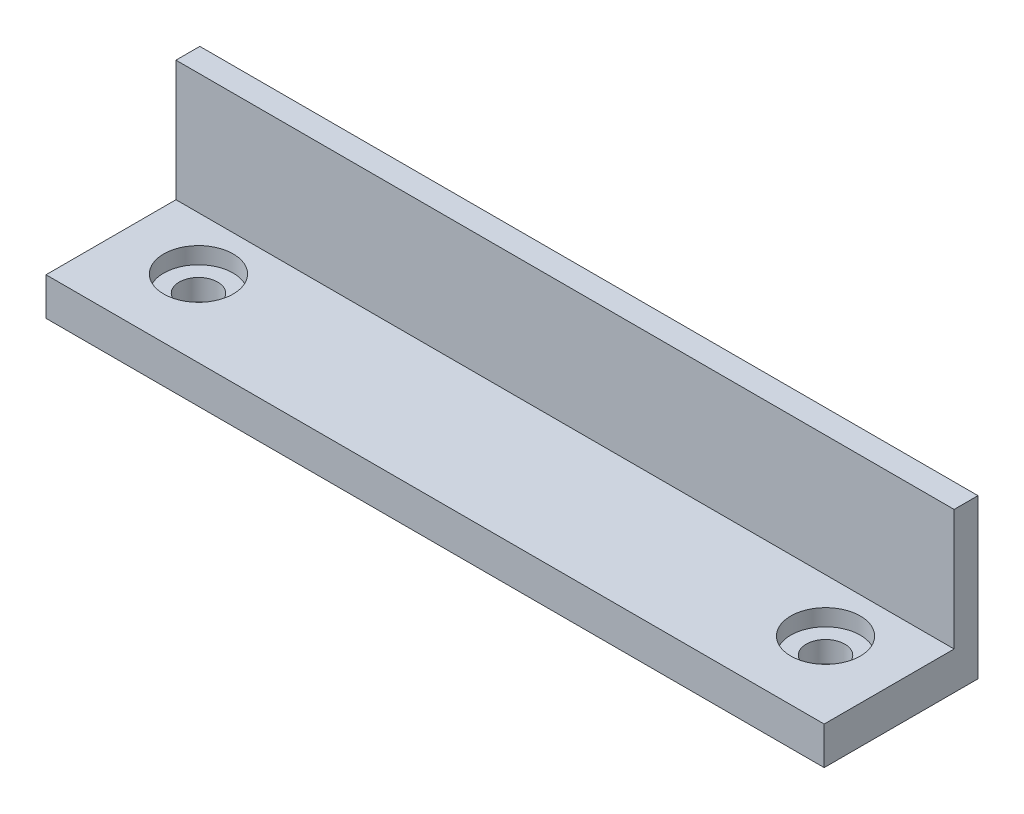
SolidWorks part; units mm, degrees
ref_plane "Front Plane" through (0, 0, 0) normal (0, 0, 1) x (1, 0, 0)
ref_plane "Top Plane" through (0, 0, 0) normal (0, 1, 0) x (1, 0, 0)
ref_plane "Right Plane" through (0, 0, 0) normal (1, 0, 0) x (0, 0, -1)
sketch "Sketch1" plane through (0, 0, 0) normal (0, 1, 0) x (1, 0, 0)
  line L0 (-51.5, 7.02) -> (51.5, 7.02)
  line L1 (-51.5, -10.18) -> (51.5, -10.18)
  line L2 (-51.5, -10.18) -> (-51.5, 10.18)
  line L3 (-51.5, 10.18) -> (51.5, 10.18)
  line L4 (51.5, -10.18) -> (51.5, 10.18)
  line L5 (-51.5, -10.18) -> (51.5, 10.18) construction
  line L6 (-51.5, 10.18) -> (51.5, -10.18) construction
  line L7 (0, 18.105) -> (0, -20.0728) construction
  circle A0 centre (41.5, 0) radius 2.55
  circle A1 centre (41.5, 0) radius 4.6
  circle A2 centre (-41.5, 0) radius 2.55
  circle A3 centre (-41.5, 0) radius 4.6
  point P0 (0, 0)
  dimension "D4" = 10
  dimension "D5" = 10.18
  dimension "D6" = 5.1
  dimension "D7" = 9.2
  dimension "D1" = 103
  dimension "D2" = 20.36
  dimension "D3" = 3.16
extrude "Boss-Extrude1" add sketch "Sketch1" along normal blind 5 contours L1 L4 L0 L2 A1 A3 | L0 L4 L3 L2 | A3 A2 | A1 A0 region at (0, 0, -8.6) region at (0, 0, 1.7082) region at (37.0301, 0, 0) region at (-45.9699, 0, 0)
extrude "Boss-Extrude2" add sketch "Sketch1<3>" along normal blind 16 from surface contours L0 L4 L3 L2 region at (0, 0, -8.6) starting at face at (0, 5, 0)
sketch "Sketch1<3>" plane through (0, 0, 0) normal (0, 1, 0) x (1, 0, 0) same geometry as "Sketch1"
extrude "Cut-Extrude1" cut sketch "Sketch1<5>" against normal blind 2.2 from surface contours A3 A2 | A1 A0 region at (37.0301, 0, 0) region at (-45.9699, 0, 0) starting at face at (-41.5, 5, 2.55)
sketch "Sketch1<5>" plane through (0, 0, 0) normal (0, 1, 0) x (1, 0, 0) same geometry as "Sketch1"
